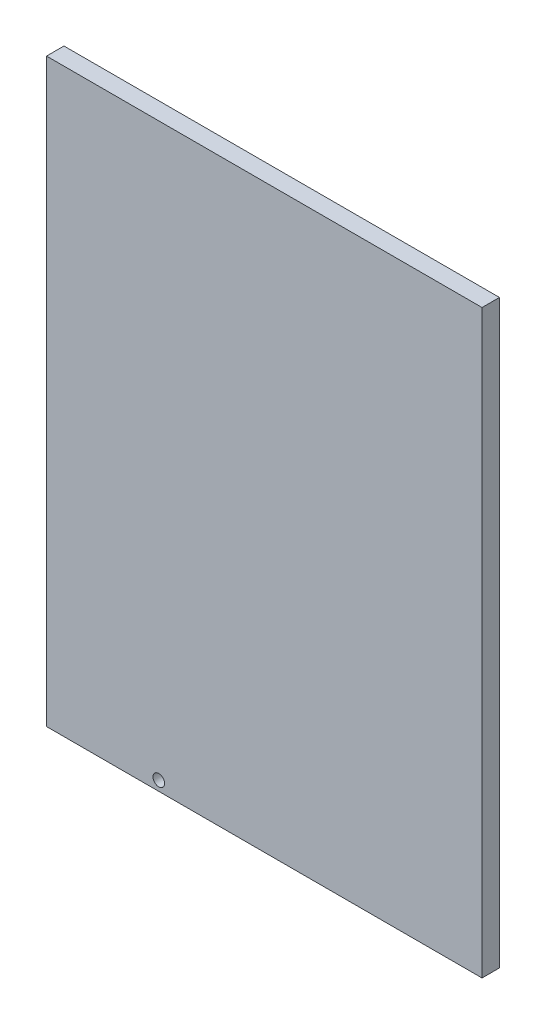
SolidWorks part; units mm, degrees
ref_plane "Front Plane" through (0, 0, 0) normal (0, 0, 1) x (1, 0, 0)
ref_plane "Top Plane" through (0, 0, 0) normal (0, 1, 0) x (1, 0, 0)
ref_plane "Right Plane" through (0, 0, 0) normal (1, 0, 0) x (0, 0, -1)
sketch "Sketch1" plane through (0, 0, 0) normal (0, 0, 1) x (1, 0, 0)
  line L1 (-112.5, -150) -> (112.5, -150)
  line L2 (-112.5, -150) -> (-112.5, 150)
  line L3 (-112.5, 150) -> (112.5, 150)
  line L4 (112.5, -150) -> (112.5, 150)
  line L5 (-112.5, -150) -> (112.5, 150) construction
  line L6 (-112.5, 150) -> (112.5, -150) construction
  point P0 (0, 0)
  dimension "D1" = 225
  dimension "D2" = 300
extrude "Boss-Extrude1" add sketch "Sketch1" along normal blind 9
sketch "Sketch2" plane through (0, 0, 9) normal (0, 0, 1) x (1, 0, 0)
  line L0 (-112.5, 150) -> (-112.5, -150) construction
  line L1 (-112.5, -150) -> (112.5, -150) construction
  circle A0 centre (-54.5, -145) radius 3
  dimension "D1" = 6
  dimension "D2" = 58
  dimension "D3" = 5
extrude "Cut-Extrude4" cut sketch "Sketch2" against normal through all
equation "\"PCWidth\"= 172mm"
equation "\"PCLength\"= 320mm"
equation "\"PCHeight\"= 242mm"
equation "\"WallThickness\"= 9mm"
equation "\"ThermoBarrierThickness\"= 3mm"
equation "\"HotSideGap\"= 50mm"
equation "\"PCClearance\"= 25mm"
equation "\"D2@Sketch1\"=\"RadiatorHeight\" + \"PCClearance\""
equation "\"D1@Sketch1\"=\"PCWidth\" + \"ThermoBarrierThickness\" + \"HotSideGap\""
equation "\"D1@Boss-Extrude1\"=\"WallThickness\""
equation "\"RadiatorHeight\"= 275mm"
equation "\"D2@Sketch2\"=\"HotSideGap\" + \"ThermoBarrierThickness\" + 5"
